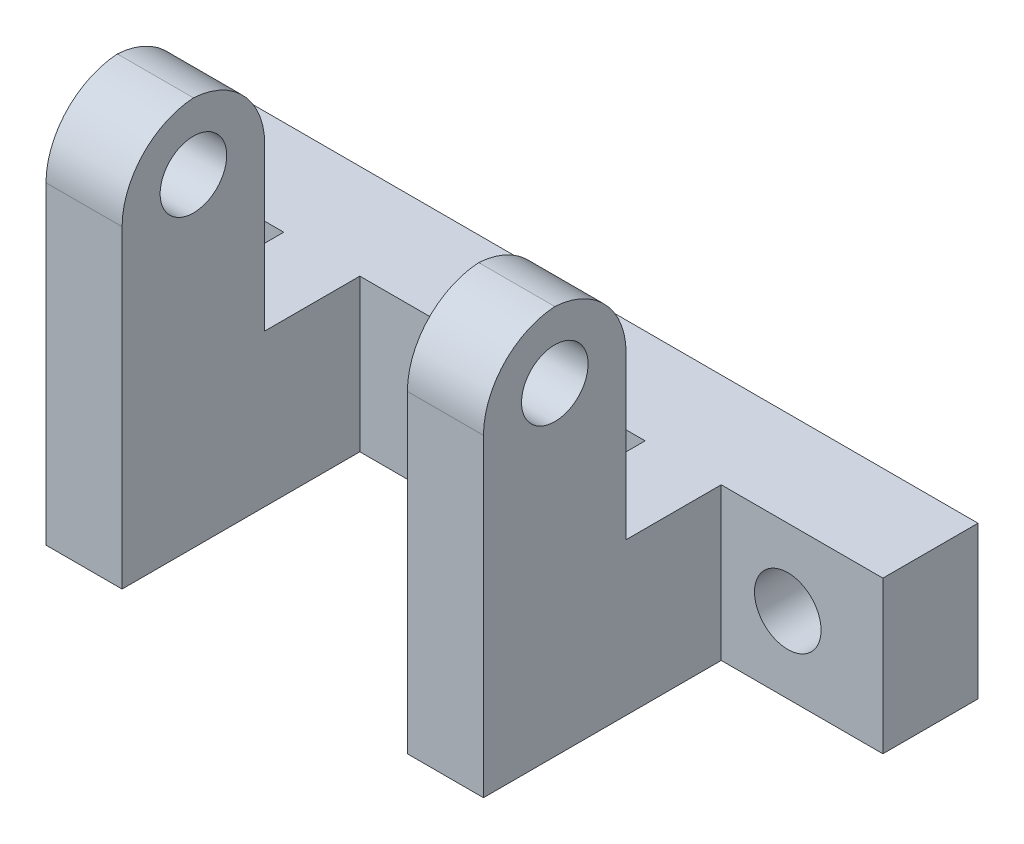
SolidWorks part; units mm, degrees
ref_plane "Front Plane" through (0, 0, 0) normal (0, 0, 1) x (1, 0, 0)
ref_plane "Top Plane" through (0, 0, 0) normal (0, 1, 0) x (1, 0, 0)
ref_plane "Right Plane" through (0, 0, 0) normal (1, 0, 0) x (0, 0, -1)
sketch "Sketch1" plane through (0, 0, 0) normal (0, 0, 1) x (1, 0, 0)
  line L0 (15, 0) -> (-15, 0) construction
  line L1 (-20, 4) -> (20, 4)
  line L2 (-20, 4) -> (-20, -4)
  line L3 (-20, -4) -> (20, -4)
  line L4 (20, 4) -> (20, -4)
  line L5 (-20, 4) -> (20, -4) construction
  line L6 (-20, -4) -> (20, 4) construction
  line L7 (0, -4) -> (0, 4) construction
  circle A0 centre (-15, 0) radius 1.75
  circle A1 centre (15, 0) radius 1.75
  point P0 (0, 0)
  point P12 (0, 0)
  dimension "D3" = 3.5
  dimension "D1" = 40
  dimension "D2" = 8
  dimension "D4" = 15
extrude "Boss-Extrude1" add sketch "Sketch1" along normal blind 5
sketch "Sketch2" plane through (0, 0, 5) normal (0, 0, 1) x (1, 0, 0)
  line L0 (0, 4) -> (0, -4) construction
  line L1 (20, 4) -> (-20, 4) construction
  line L2 (-20, -4) -> (20, -4) construction
  line L3 (11.5, -4) -> (7.5, 4) construction
  line L4 (-11.5, 4) -> (-7.5, 4)
  line L5 (-11.5, 4) -> (-11.5, -4)
  line L6 (-11.5, -4) -> (-7.5, -4)
  line L7 (-7.5, 4) -> (-7.5, -4)
  line L8 (-11.5, 4) -> (-7.5, -4) construction
  line L9 (-11.5, -4) -> (-7.5, 4) construction
  line L10 (11.5, 4) -> (7.5, -4) construction
  line L11 (7.5, 4) -> (7.5, -4)
  line L12 (11.5, -4) -> (7.5, -4)
  line L13 (11.5, 4) -> (11.5, -4)
  line L14 (11.5, 4) -> (7.5, 4)
  point P6 (-9.5, 0)
  point P15 (9.5, 0)
  dimension "D1" = 7.5
  dimension "D2" = 4
extrude "Boss-Extrude2" add sketch "Sketch2" along normal blind 12.5
sketch "Sketch4" plane through (0, 4, 0) normal (0, 1, 0) x (1, 0, 0)
  line L0 (-7.5, -17.5) -> (-7.5, -5) construction
  line L1 (-11.5, -17.5) -> (-7.5, -17.5)
  line L2 (-11.5, -17.5) -> (-11.5, -10)
  line L3 (-11.5, -10) -> (-7.5, -10)
  line L4 (-7.5, -17.5) -> (-7.5, -10)
  line L5 (0, 0) -> (0, -5) construction
  line L6 (7.5, -5) -> (-7.5, -5) construction
  line L7 (7.5, -17.5) -> (7.5, -10)
  line L8 (11.5, -10) -> (7.5, -10)
  line L9 (11.5, -17.5) -> (11.5, -10)
  line L10 (11.5, -17.5) -> (7.5, -17.5)
  dimension "D1" = 7.5
extrude "Boss-Extrude3" add sketch "Sketch4" along normal blind 12.5
sketch "Sketch3" plane through (-11.5, 0, 0) normal (-1, 0, 0) x (0, 0, 1)
  line L0 (10, 13) -> (17.5, 13) construction
  line L4 (10, 16.5) -> (10, 4) construction
  line L5 (17.5, 16.5) -> (17.5, -4) construction
  line L6 (13.75, 13) -> (13.75, 16.5) construction
  line L7 (10, 16.5) -> (17.5, 16.5) construction
  circle A0 centre (13.75, 13) radius 1.75
  dimension "D1" = 3.5
  dimension "D2" = 13
extrude "Cut-Extrude1" cut sketch "Sketch3" against normal through all
fillet "Fillet1" radius 4 4 edges at (-9.5, 16.5, 10) (9.5, 16.5, 10) (9.5, 16.5, 17.5) (-9.5, 16.5, 17.5)
equation "\"X-ROD-SPACING\"=45"
equation "\"Y-ROD-SPACING\"=75"
equation "\"Z-ROD-SPACING\"=17.5"
equation "\"Y-BED-OFFSET\"=2"
equation "\"Y-BED-ROD-INSET\"=3.5"
equation "\"Y-BED-SCREW-SPACING\"=209"
equation "\"Y-BED-SCREW-CUTOUT-SLOT-HEIGHT\"=1"
equation "\"T-SLOT-NUT-FILLET-RADIUS\"=0.25"
equation "\"T-SLOT-SCREW-SHAFT-RADIUS\"=1.75"
equation "\"T-SLOT-SCREW-SHAFT-CUTOUT-LENGTH\"=10.5"
equation "\"T-SLOT-NUT-DEPTH\"=4.2"
equation "\"T-SLOT-NUT-WIDTH\"=3"
equation "\"T-SLOT-NUT-END-DISTANCE\"=8"
equation "\"ACRYLIC-THICKNESS\"=10"
equation "\"ACRYLIC-THICKNESS2\"=4.5"
equation "\"ACRYLIC-TAB-CUTOUT-SIZE\"=\"ACRYLIC-THICKNESS\"+\"ACRYLIC-TAB-TOLERANCE\"*2"
equation "\"ACRYLIC-TAB-TOLERANCE\"=.1"
equation "\"ACRYLIC-TAB-WIDTH\"=\"ACRYLIC-THICKNESS\""
equation "\"ACRYLIC-M3-HOLE\"=3.1"
equation "\"SMOOTHROD-CAP-SCREW-DISTANCE\"=20"
equation "\"FRAME-WIDTH-INNER\"=370"
equation "\"NEMA17-HOLE-SPACING\"=31"
equation "\"NEMA17-CENTRAL-CUTOUT\"=22.5"
equation "\"Z-BRACKET-REACH\"=55"
equation "\"Z-ROD-INSET\"=16"
equation "\"TOP-BRACKET-SPACING\"=40"
equation "\"SMOOTHROD-X-LENGTH\"=350"
equation "\"SMOOTHROD-Y-LENGTH\"=350"
equation "\"SMOOTHROD-Z-LENGTH\"=350"
equation "\"SMOOTHROD-TIGHTENING-HEADROOM\"=1"
equation "\"LEADSCREW-Z-LENGTH\"=300"
equation "\"SCREW-LENGTH-FRAME\"=\"ACRYLIC-THICKNESS\" + 10"
equation "\"SCREW-LENGTH-MOTOR\"=\"ACRYLIC-THICKNESS\" + 5"
equation "\"SCREW-LENGTH-EXTRUDER\"=28"
equation "\"SCREW-HEAD-RADIUS\"=6"
equation "\"PRINTED-X-SMOOTHROD-DIAMETER\"=8.2"
equation "\"PRINTED-X-SMOOTHROD-CUTOUT\"=10"
equation "\"PRINTED-X-BASE-HEIGHT\"=10"
equation "\"PRINTED-LM8UU-CUTOUT-SIZE\"=15.25"
equation "\"PRINTED-LM8UU-CUTOUT-LENGTH\"=24.5"
equation "\"PRINTED-X-IDLER-HEIGHT\"=16"
equation "\"PSU-MOUNTING-WIDTH\"=95"
equation "\"PSU-MOUNTING-HEIGHT\"=177"
equation "\"Y-BELT-TO-ROD-DISTANCE\"=20"
equation "\"SPOOL-HOLDER-ROD-SPACING\"=150"
equation "\"ACRYLIC-X-CARRIAGE-WIDTH\"=55"
equation "\"ACRYLIC-X-CARRIAGE-HEIGHT\"=75"
equation "\"ACRYLIC-X-CARRIAGE-LM8UU-CUTOUT-WIDTH\"=24.25"
equation "\"ACRYLIC-X-CARRIAGE-LM8UU-CUTOUT-HEIGHT\"=11.5"
equation "\"ACRYLIC-X-CARRIAGE-SCREW-SPACING-X\"=15"
equation "\"ACRYLIC-X-CARRIAGE-SCREW-SPACING-Y\"=33"
equation "\"ACRYLIC-X-CARRIAGE-CENTER-TAB-SPACING\"=14"
equation "\"ACRYLIC-X-CARRIAGE-EXTRUDER-OFFSET\"=26"
equation "\"ACRYLIC-X-CARRIAGE-EXTRUDER-ANGLE\"=90"
equation "\"ACRYLIC-X-CARRIAGE-EXTRUDER-SHELF-DEPTH\"=\"ACRYLIC-X-CARRIAGE-EXTRUDER-OFFSET\" + 30"
equation "\"ACRYLIC-X-CARRIAGE-EXTRUDER-BRACE-SPACING\"=23"
equation "\"ACRYLIC-X-CARRIAGE-EXTRUDER-BRACE-TAB-OFFSET\"=20"
equation "\"ACRYLIC-X-CARRIAGE-EXTRUDER-BRACE-HEIGHT\"=35"
equation "\"ACRYLIC-X-CARRIAGE-EXTRUDER-BRACE-SCREW-SPACING\"=22"
equation "\"ACRYLIC-X-CARRIAGE-DUAL-WIDTH-MULTIPLIER\"=1.65"
equation "\"ACRYLIC-X-CARRIAGE-DUAL-HOTEND-SPACING\"=42"
equation "\"ACRYLIC-X-CARRIAGE-DUAL-WIDTH\"=103"
equation "\"ACRYLIC-X-CARRIAGE-DUAL-HOTEND-SEPARATION\"=35"
equation "\"ACRYLIC-X-CARRIAGE-DUAL-MOUNT-PLATE-DEPTH\"=76"
equation "\"ACRYLIC-X-CARRIAGE-DUAL-MOUNT-BRACE-WIDTH\"=45"
equation "\"ACRYLIC-X-CARRIAGE-DUAL-MOUNT-SCREW-WIDTH\"=40"
equation "\"D3@Sketch1\"=3.5"
equation "\"PRINTED-M3-HOLE\"=3.5"
equation "\"BLOWER-FAN-WIDTH\"=15"
equation "\"D1@Sketch2\"=\"BLOWER-FAN-WIDTH\"/2"
